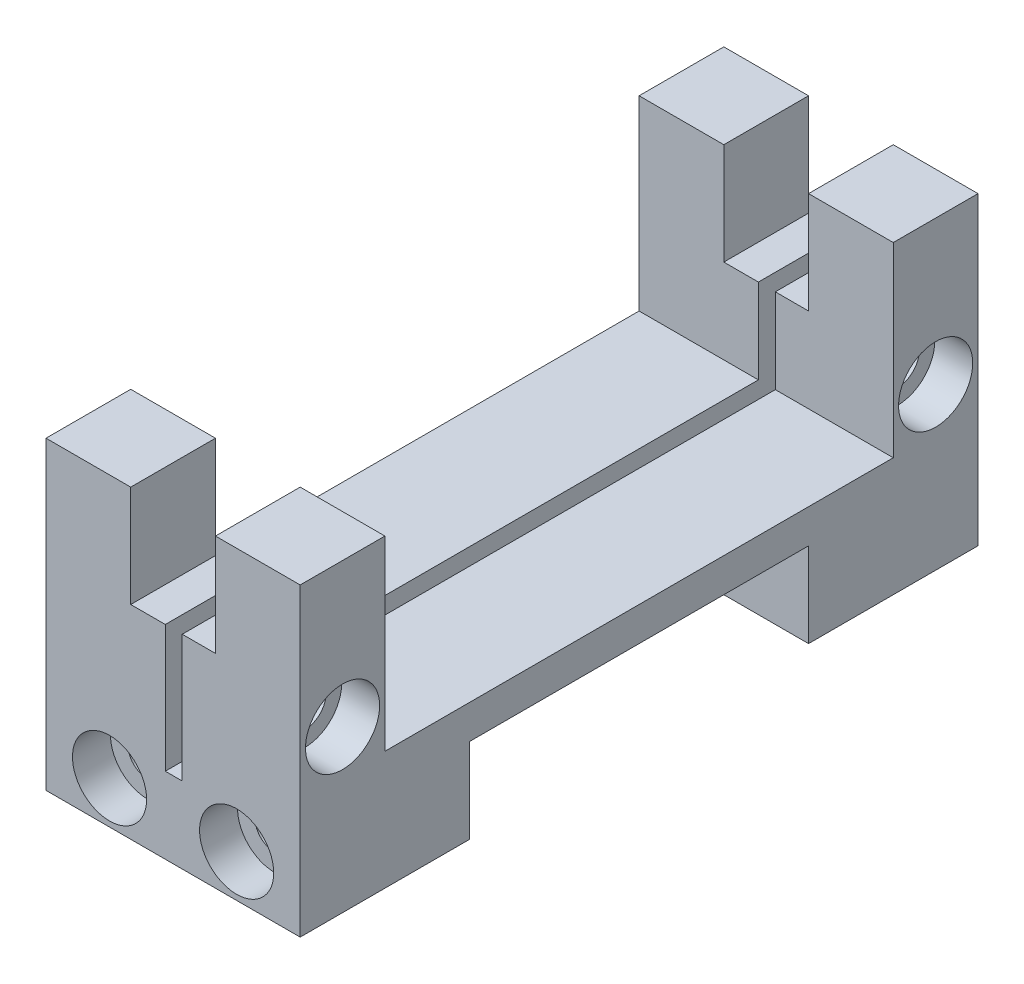
SolidWorks part; units mm, degrees
material "6061 Alloy"
ref_plane "Front Plane" through (0, 0, 0) normal (0, 0, 1) x (1, 0, 0)
ref_plane "Top Plane" through (0, 0, 0) normal (0, 1, 0) x (1, 0, 0)
ref_plane "Right Plane" through (0, 0, 0) normal (1, 0, 0) x (0, 0, -1)
sketch "Sketch2" plane through (0, 0, 0) normal (0, 0, 1) x (1, 0, 0)
  line L1 (-9.525, -9.525) -> (9.525, -9.525)
  line L2 (-9.525, -9.525) -> (-9.525, 9.525)
  line L3 (-9.525, 9.525) -> (9.525, 9.525)
  line L4 (9.525, -9.525) -> (9.525, 9.525)
  line L5 (-9.525, -9.525) -> (9.525, 9.525) construction
  line L6 (-9.525, 9.525) -> (9.525, -9.525) construction
  point P0 (0, 0)
  dimension "D1" = 19.05
  dimension "D2" = 19.05
extrude "Boss-Extrude1" add sketch "Sketch2" along normal mid plane 50.8
sketch "Sketch4" plane through (-1.5069, 3.1105, 25.4) normal (0, 0, 1) x (1, 0, 0)
  line L1 (-1.6681, 6.4145) -> (4.6819, 6.4145)
  line L2 (-1.6681, 6.4145) -> (-1.6681, -3.7455)
  line L3 (-1.6681, -3.7455) -> (4.6819, -3.7455)
  line L4 (4.6819, 6.4145) -> (4.6819, -3.7455)
  line L7 (-8.0181, 6.4145) -> (11.0319, 6.4145)
  line L8 (-8.0181, 6.4145) -> (-8.0181, 3.8745)
  line L9 (-8.0181, 3.8745) -> (11.0319, 3.8745)
  line L10 (11.0319, 6.4145) -> (11.0319, 3.8745)
  line L11 (11.0319, 6.4145) -> (-8.0181, 6.4145) construction
  line L12 (11.0319, -12.6355) -> (11.0319, 6.4145) construction
  line L13 (-8.0181, 6.4145) -> (-8.0181, -12.6355) construction
  dimension "D1" = 6.35
  dimension "D2" = 0
  dimension "D3" = 10.16
  dimension "D4" = 2.54
  dimension "D5" = 0
  dimension "D6" = 0
  dimension "D7" = 0
  dimension "D8" = 6.35
extrude "Cut-Extrude1" cut sketch "Sketch4" against normal through all contours L4 L9 | L2 L9 L4 | L9 L2 L3 L4 | L9 L2 region at (0, 8.255, 25.4) region at (-6.35, 8.255, 25.4) region at (6.35, 8.255, 25.4) region at (0, 3.175, 25.4)
sketch "Sketch7" plane through (9.525, 0, 0) normal (1, 0, 0) x (0, 0, -1)
  line L0 (25.4, 6.985) -> (-25.4, 6.985) construction
  line L1 (-19.05, 6.985) -> (19.05, 6.985)
  line L2 (-19.05, 6.985) -> (-19.05, -6.985)
  line L3 (-19.05, -6.985) -> (19.05, -6.985)
  line L4 (19.05, 6.985) -> (19.05, -6.985)
  line L5 (-25.4, -9.525) -> (-25.4, 6.985) construction
  line L6 (25.4, -9.525) -> (25.4, 6.985) construction
  line L7 (-25.4, -9.525) -> (25.4, -9.525) construction
  dimension "D1" = 6.35
  dimension "D2" = 6.35
  dimension "D3" = 2.54
extrude "Cut-Extrude3" cut sketch "Sketch7" against normal through all
sketch "Sketch8" plane through (0, 0, 25.4) normal (0, 0, 1) x (1, 0, 0)
  line L0 (-9.525, -9.525) -> (9.525, -9.525)
  line L1 (-9.525, -9.525) -> (-9.525, -15.875)
  line L2 (9.525, -9.525) -> (9.525, -15.875)
  line L3 (-9.525, -15.875) -> (9.525, -15.875)
  dimension "D1" = 6.35
extrude "Boss-Extrude2" add sketch "Sketch8" against normal blind 12.7
mirror "Mirror1" about plane through (0, 0, 0) normal (0, 0, 1) of "Boss-Extrude2"
hole_wizard "CBORE for #4 Socket Head Cap Screw1" positions "Sketch9" profile "Sketch10" counterbore size "#4" standard "ANSI Inch" end condition up to next
sketch "Sketch9" plane through (0, 0, 25.4) normal (0, 0, 1) x (1, 0, 0)
  line L0 (-9.525, -15.875) -> (9.525, -15.875) construction
  line L1 (-9.525, 6.985) -> (-9.525, -15.875) construction
  line L2 (9.525, -15.875) -> (9.525, 6.985) construction
  point P0 (-4.7625, -12.7)
  point P2 (4.7625, -12.7)
  dimension "D1" = 3.175
  dimension "D2" = 4.7625
  dimension "D3" = 4.7625
  dimension "D4" = 3.175
sketch "Sketch10" plane through (-4.7625, -12.7, 25.4) normal (1, 0, 0) x (0, -1, 0)
  line L0 (0, 0) -> (0, 12.7)
  line L1 (0, 12.7) -> (1.4732, 12.7)
  line L3 (1.4732, 12.7) -> (1.4732, 2.8448)
  line L4 (1.4732, 2.8448) -> (2.7788, 2.8448)
  line L5 (2.7788, 2.8448) -> (2.7788, 0)
  line L7 (2.7788, 0) -> (0, 0)
  line L11 (0, -6.35) -> (0, 107.95) construction
  dimension "Thru Hole Dia." = 2.9464
  dimension "Thru Hole Depth" = 12.7
  dimension "C'Bore Dia." = 5.5575
  dimension "C'Bore Depth" = 2.8448
sketch "Sketch11" plane through (0, 0, 25.4) normal (0, 0, 1) x (1, 0, 0)
  line L0 (-3.175, -0.635) -> (3.175, -0.635) construction
  line L1 (-0.5848, -0.635) -> (0.6852, -0.635)
  line L2 (-0.5848, -0.635) -> (-0.5848, -10.16)
  line L3 (-0.5848, -10.16) -> (0.6852, -10.16)
  line L4 (0.6852, -0.635) -> (0.6852, -10.16)
  line L5 (-0.5848, -0.635) -> (0.6852, -10.16) construction
  line L6 (-0.5848, -10.16) -> (0.6852, -0.635) construction
  point P0 (0.0502, -5.3975)
  dimension "D1" = 1.27
  dimension "D2" = 0
  dimension "D3" = 9.525
extrude "Cut-Extrude4" cut sketch "Sketch11" against normal through all
hole_wizard "CBORE for #4 Socket Head Cap Screw2" positions "Sketch12" profile "Sketch13" counterbore size "#4" standard "ANSI Inch" end condition up to next
sketch "Sketch12" plane through (9.525, 0, 0) normal (1, 0, 0) x (0, 0, -1)
  line L0 (-19.05, 6.985) -> (-19.05, -6.985) construction
  line L1 (19.05, -6.985) -> (19.05, 6.985) construction
  point P0 (-22.225, -3.81)
  point P2 (22.225, -3.81)
  dimension "D1" = 3.175
  dimension "D2" = 3.175
  dimension "D3" = 3.175
  dimension "D4" = 3.175
sketch "Sketch13" plane through (9.525, -3.81, 22.225) normal (0, 1, 0) x (0, 0, -1)
  line L0 (0, 0) -> (0, 8.8398)
  line L1 (0, 8.8398) -> (1.6319, 8.8398)
  line L3 (1.6319, 8.8398) -> (1.6319, 2.8448)
  line L4 (1.6319, 2.8448) -> (2.7788, 2.8448)
  line L5 (2.7788, 2.8448) -> (2.7788, 0)
  line L7 (2.7788, 0) -> (0, 0)
  line L11 (0, -6.35) -> (0, 107.95) construction
  dimension "Thru Hole Dia." = 3.2639
  dimension "Thru Hole Depth" = 8.8398
  dimension "C'Bore Dia." = 5.5575
  dimension "C'Bore Depth" = 2.8448
hole_wizard "#4-40 Tapped Hole1" positions "Sketch14" profile "Sketch15" tap size "#4-40" standard "ANSI Inch" end condition up to next
sketch "Sketch14" plane through (-0.5848, 0, 0) normal (1, 0, 0) x (0, 0, -1)
  point P0 (-22.225, -3.81)
  point P3 (22.225, -3.81)
sketch "Sketch15" plane through (-0.5848, -3.81, 22.225) normal (0, 1, 0) x (0, 0, -1)
  line L0 (0, 0) -> (0, 8.9402)
  line L1 (0, 8.9402) -> (1.1303, 8.9402)
  line L2 (1.1303, 8.9402) -> (1.1303, 0)
  line L5 (1.1303, 0) -> (0, 0)
  line L11 (0, -6.35) -> (0, 107.95) construction
  dimension "Thru Tap Drill Dia." = 2.2606
  dimension "Thru Tap Drill Depth" = 8.9402
cosmetic thread "Hole Thread1" parameters "D2"=2.8448
cosmetic thread "Hole Thread2" parameters "D2"=2.8448
